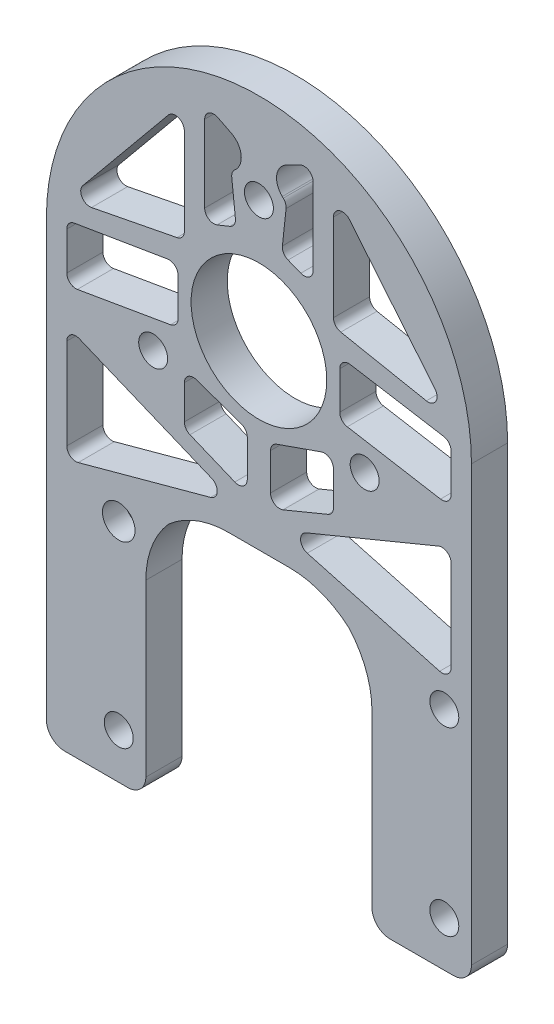
SolidWorks part; units mm, degrees
material "Hexcel AS4C (3000 丝)"
ref_plane "前视基准面" through (0, 0, 0) normal (0, 0, 1) x (1, 0, 0)
ref_plane "上视基准面" through (0, 0, 0) normal (0, 1, 0) x (1, 0, 0)
ref_plane "右视基准面" through (0, 0, 0) normal (1, 0, 0) x (0, 0, -1)
sketch "草图1" plane through (0, 0, 0) normal (0, 0, 1) x (1, 0, 0)
  line L0 (-23.5, 0) -> (-23.5, -50)
  line L1 (-23.5, -50) -> (23.5, -50)
  line L2 (23.5, -50) -> (23.5, 0)
  line L3 (0, 0) -> (0, -50) construction
  circle A0 centre (0, 0) radius 13.5 construction
  circle A1 centre (0, 13.5) radius 1.6
  circle A2 centre (11.6913, -6.75) radius 1.6
  circle A3 centre (-11.6913, -6.75) radius 1.6
  arc A4 (23.5, 0) -> (-23.5, 0) centre (0, 0) ccw
  circle A5 centre (4.5, -47) radius 1.6 construction
  circle A6 centre (-15.5, -47) radius 1.6 construction
  circle A7 centre (0, 0) radius 7.5
  point P11 (0, 0)
  dimension "D1" = 27
  dimension "D2" = 3.2
  dimension "D4" = 47
  dimension "D6" = 3.2
  dimension "D7" = 20
  dimension "D8" = 3
  dimension "D9" = 15
  dimension "D10" = 8
  dimension "D5" = 50
  dimension "D3" = 3
extrude "凸台-拉伸1" add sketch "草图1" along normal blind 4
fillet "圆角1" [suppressed] radius 4
sketch "草图2" plane through (0, 0, 4) normal (0, 0, 1) x (1, 0, 0)
  line L0 (20.5, -25) -> (20.5, -45) construction
  line L1 (-23.5, 0) -> (-23.5, -50) construction
  line L2 (-23.5, -50) -> (23.5, -50) construction
  line L3 (23.5, -50) -> (23.5, 0) construction
  line L4 (0, 0) -> (0, -50) construction
  line L5 (-15.5, -25) -> (-15.5, -45) construction
  circle A0 centre (20.5, -45) radius 1.6
  circle A1 centre (20.5, -25) radius 1.6
  circle A2 centre (-15.5, -45) radius 1.6
  circle A3 centre (-15.5, -25) radius 1.6
  dimension "D2" = 3.2
  dimension "D3" = 5
  dimension "D6" = 3.2
  dimension "D7" = 5
  dimension "D1" = 20
  dimension "D4" = 3
  dimension "D5" = 20
  dimension "D8" = 8
  dimension "D9" = 20.5
extrude "切除-拉伸1" cut sketch "草图2" against normal through all
sketch "草图3" plane through (0, 0, 4) normal (0, 0, 1) x (1, 0, 0)
  line L0 (0, 0) -> (0, -50) construction
  line L1 (-23.5, -50) -> (23.5, -50) construction
  line L2 (12.5, -25) -> (7.5, -20)
  line L3 (7.5, -20) -> (-7.5, -20)
  line L4 (12.5, -25) -> (12.5, -50)
  line L5 (12.5, -50) -> (-12.5, -50)
  line L6 (-12.5, -25) -> (-12.5, -50)
  line L7 (12.5, -20) -> (-12.5, -50) construction
  line L8 (12.5, -50) -> (-12.5, -20) construction
  line L9 (-7.5, -20) -> (-12.5, -25)
  point P5 (0, -35)
  dimension "D1" = 25
  dimension "D2" = 30
extrude "切除-拉伸2" cut sketch "草图3" against normal through all
fillet "圆角2" radius 10 4 edges at (-12.5, -25, 2) (-7.5, -20, 2) (7.5, -20, 2) (12.5, -25, 2)
fillet "圆角3" radius 2 4 edges at (-23.5, -50, 2) (23.5, -50, 2) (-12.5, -50, 2) (12.5, -50, 2)
sketch "草图4" plane through (0, 0, 4) normal (0, 0, 1) x (1, 0, 0)
  line L0 (8.243, 18.7931) -> (21.246, 3.0038)
  line L1 (21.246, 3.0038) -> (8.243, 5.5443)
  line L2 (8.243, 5.5443) -> (8.243, 18.7931)
  line L3 (5.9984, 19.8767) -> (5.9984, 8.2669)
  line L4 (5.9984, 8.2669) -> (2.5155, 9.6601)
  line L5 (2.5155, 9.6601) -> (3.0573, 14.691)
  line L6 (3.0573, 14.691) -> (0.5031, 17.0903)
  line L7 (0.5031, 17.0903) -> (5.9984, 19.8767)
  line L8 (21.246, 0.9539) -> (21.246, -5.2864)
  line L9 (21.246, -5.2864) -> (8.9394, -3.1757)
  line L10 (8.9394, -3.1757) -> (8.9394, 3.0038)
  line L11 (8.9394, 3.0038) -> (21.246, 0.9539)
  line L12 (0, 0) -> (0, -27.1529) construction
  line L13 (21.246, -9.1278) -> (21.246, -21.9638)
  line L14 (21.246, -21.9638) -> (2.5155, -16.8658)
  line L15 (2.5155, -16.8658) -> (21.246, -9.1278)
  line L16 (8.243, -6.687) -> (8.243, -12.5195)
  line L17 (8.243, -12.5195) -> (1.2854, -15.3938)
  line L18 (1.2854, -15.3938) -> (1.2854, -9.1278)
  line L19 (1.2854, -9.1278) -> (8.243, -6.687)
  line L20 (-3.0573, 14.691) -> (-0.5031, 17.0903)
  line L21 (-2.5155, 9.6601) -> (-3.0573, 14.691)
  line L22 (-5.9984, 8.2669) -> (-2.5155, 9.6601)
  line L23 (-5.9984, 19.8767) -> (-5.9984, 8.2669)
  line L24 (-0.5031, 17.0903) -> (-5.9984, 19.8767)
  line L25 (-21.246, 3.0038) -> (-8.243, 5.5443)
  line L26 (-8.243, 18.7931) -> (-21.246, 3.0038)
  line L27 (-8.243, 5.5443) -> (-8.243, 18.7931)
  line L28 (-8.9394, -3.1757) -> (-8.9394, 3.0038)
  line L29 (-21.246, -5.2864) -> (-8.9394, -3.1757)
  line L30 (-21.246, 0.9539) -> (-21.246, -5.2864)
  line L31 (-8.9394, 3.0038) -> (-21.246, 0.9539)
  line L32 (-21.246, -21.9638) -> (-2.5155, -16.8658)
  line L33 (-21.246, -9.1278) -> (-21.246, -21.9638)
  line L34 (-2.5155, -16.8658) -> (-21.246, -9.1278)
  line L35 (-1.2854, -15.3938) -> (-1.2854, -9.1278)
  line L36 (-8.243, -12.5195) -> (-1.2854, -15.3938)
  line L37 (-8.243, -6.687) -> (-8.243, -12.5195)
  line L38 (-1.2854, -9.1278) -> (-8.243, -6.687)
extrude "切除-拉伸3" cut sketch "草图4" against normal through all
fillet "圆角4" radius 2 2 edges at (0.5031, 17.0903, 2) (-0.5031, 17.0903, 2)
fillet "圆角5" radius 1 36 edges at (21.246, 3.0038, 2) (8.243, 5.5443, 2) (8.243, 18.7931, 2) (-8.243, -6.687, 2) (-1.2854, -9.1278, 2) (-1.2854, -15.3938, 2) (-8.243, -12.5195, 2) (-5.9984, 8.2669, 2) (-5.9984, 19.8767, 2) (-3.0573, 14.691, 2) (-2.5155, 9.6601, 2) (-8.243, 5.5443, 2) (-21.246, 3.0038, 2) (-8.243, 18.7931, 2) (-21.246, 0.9539, 2) (-8.9394, 3.0038, 2) (-8.9394, -3.1757, 2) (-21.246, -5.2864, 2) (-2.5155, -16.8658, 2) (-21.246, -21.9638, 2) (-21.246, -9.1278, 2) (21.246, -21.9638, 2) (2.5155, -16.8658, 2) (21.246, -9.1278, 2) (8.243, -12.5195, 2) (1.2854, -15.3938, 2) (1.2854, -9.1278, 2) (8.243, -6.687, 2) (21.246, -5.2864, 2) (8.9394, -3.1757, 2) (8.9394, 3.0038, 2) (21.246, 0.9539, 2) (2.5155, 9.6601, 2) (3.0573, 14.691, 2) (5.9984, 8.2669, 2) (5.9984, 19.8767, 2)
hole_wizard "M3 十字槽半沉头木螺钉的锥形沉头孔1" positions "草图5" profile "草图6" countersink size "M3" standard "GB" end condition through all
sketch "草图5" plane through (0, 0, 0) normal (0, 0, -1) x (-1, 0, 0)
  point P0 (15.5, -25)
sketch "草图6" plane through (-15.5, -25, 0) normal (1, 0, 0) x (0, 1, 0)
  line L0 (0, 0) -> (0, 4)
  line L1 (0, 4) -> (1.8, 4)
  line L2 (1.8, 4) -> (1.8, 1.5)
  line L3 (1.8, 1.5) -> (3.3, 0)
  line L5 (3.3, 0) -> (0, 0)
  line L6 (-1.8, 1.5) -> (-3.3, 0) construction
  line L11 (0, -6.35) -> (0, 107.95) construction
  dimension "通孔孔直径" = 3.6
  dimension "通孔孔深度" = 4
  dimension "近端锥形沉头孔直径" = 6.6
  dimension "近端锥形沉头孔角度" = 90
